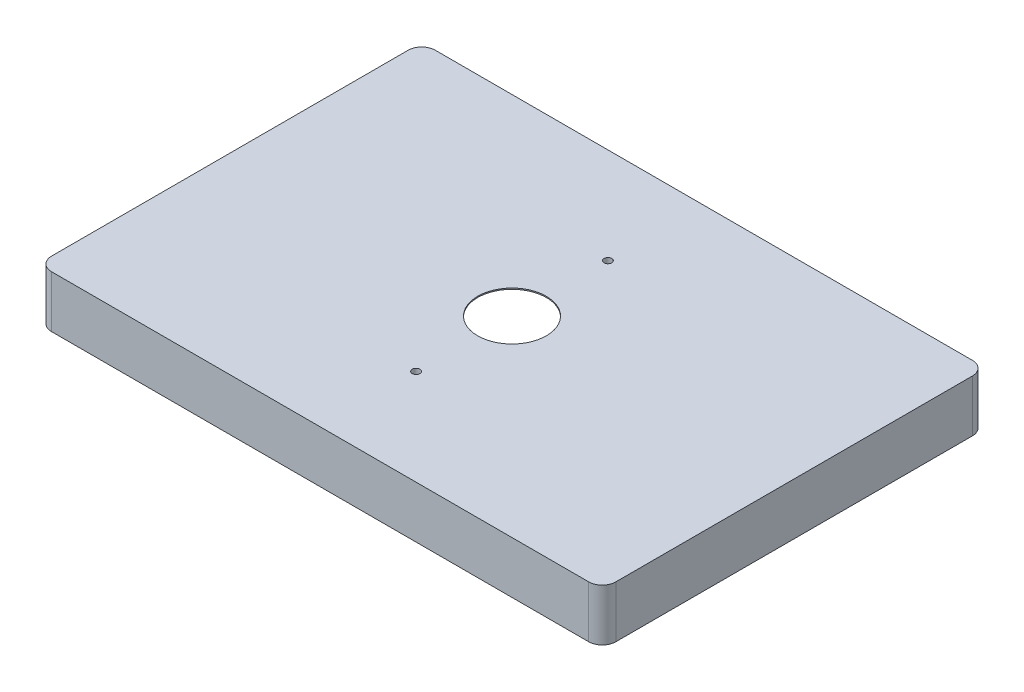
SolidWorks part; units mm, degrees
ref_plane "Front Plane" through (0, 0, 0) normal (0, 0, 1) x (1, 0, 0)
ref_plane "Top Plane" through (0, 0, 0) normal (0, 1, 0) x (1, 0, 0)
ref_plane "Right Plane" through (0, 0, 0) normal (1, 0, 0) x (0, 0, -1)
sketch "Sketch1" plane through (0, 0, 0) normal (0, 1, 0) x (1, 0, 0)
  line L1 (125, -85) -> (-125, -85)
  line L2 (125, -85) -> (125, 85)
  line L3 (125, 85) -> (-125, 85)
  line L4 (-125, -85) -> (-125, 85)
  line L5 (125, -85) -> (-125, 85) construction
  line L6 (125, 85) -> (-125, -85) construction
  circle A0 centre (0, 0) radius 15.2
  point P0 (0, 0)
  dimension "D3" = 30.4
  dimension "D1" = 170
  dimension "D2" = 250
extrude "Boss-Extrude1" add sketch "Sketch1" against normal blind 10
fillet "Fillet1" radius 6 4 edges at (-125, -5, -85) (-125, -5, 85) (125, -5, 85) (125, -5, -85)
sketch "Sketch3" plane through (0, -10, 0) normal (0, -1, 0) x (1, 0, 0)
  line L8 (-121, 79) -> (-121, -79)
  line L9 (-119, -81) -> (119, -81)
  line L10 (121, -79) -> (121, 79)
  line L11 (119, 81) -> (-119, 81)
  line L12 (-121, 79) -> (-121, -79)
  line L13 (-119, -81) -> (119, -81)
  line L14 (121, -79) -> (121, 79)
  line L15 (119, 81) -> (-119, 81)
  line L16 (-125, 79) -> (-125, -79)
  line L17 (-119, -85) -> (119, -85)
  line L18 (125, -79) -> (125, 79)
  line L19 (119, 85) -> (-119, 85)
  line L20 (-125, 79) -> (-125, -79)
  line L21 (-119, -85) -> (119, -85)
  line L22 (125, -79) -> (125, 79)
  line L23 (119, 85) -> (-119, 85)
  arc A4 (-121, -79) -> (-119, -81) centre (-119, -79) ccw
  arc A5 (119, -81) -> (121, -79) centre (119, -79) ccw
  arc A6 (121, 79) -> (119, 81) centre (119, 79) ccw
  arc A7 (-121, 79) -> (-119, 81) centre (-119, 79) cw
  arc A12 (-125, -79) -> (-119, -85) centre (-119, -79) ccw
  arc A13 (119, -85) -> (125, -79) centre (119, -79) ccw
  arc A14 (125, 79) -> (119, 85) centre (119, 79) ccw
  arc A15 (-119, 85) -> (-125, 79) centre (-119, 79) ccw
  arc A16 (-125, -79) -> (-119, -85) centre (-119, -79) ccw
  arc A17 (119, -85) -> (125, -79) centre (119, -79) ccw
  arc A18 (125, 79) -> (119, 85) centre (119, 79) ccw
  arc A19 (-119, 85) -> (-125, 79) centre (-119, 79) ccw
  arc A20 (-121, -79) -> (-119, -81) centre (-119, -79) ccw
  arc A21 (-121, -79) -> (-119, -81) centre (-119, -79) ccw
  arc A22 (119, -81) -> (121, -79) centre (119, -79) ccw
  arc A23 (119, -81) -> (121, -79) centre (119, -79) ccw
  arc A24 (121, 79) -> (119, 81) centre (119, 79) ccw
  arc A25 (121, 79) -> (119, 81) centre (119, 79) ccw
  arc A26 (-119, 81) -> (-121, 79) centre (-119, 79) ccw
  arc A27 (-119, 81) -> (-121, 79) centre (-119, 79) ccw
  line M14 (-125, 79) -> (-125, -79)
  arc M15 (-125, -79) -> (-119, -85) centre (-119, -79) ccw
  line M16 (-119, -85) -> (119, -85)
  arc M17 (119, -85) -> (125, -79) centre (119, -79) ccw
  line M18 (125, -79) -> (125, 79)
  arc M19 (125, 79) -> (119, 85) centre (119, 79) ccw
  line M20 (119, 85) -> (-119, 85)
  arc M21 (-119, 85) -> (-125, 79) centre (-119, 79) ccw
  dimension "D2" = 2
  dimension "D1" = 4
  dimension "D3" = 0
extrude "Boss-Extrude2" add sketch "Sketch3" along normal blind 13 contours L12 A7 L15 A6 L14 A5 L13 A4 M21 M14 M15 M16 M17 M18 M19 M20 | L20 A16 L21 A17 L22 A18 L23 A19
sketch "Sketch4" plane through (0, -10, 0) normal (0, -1, 0) x (1, 0, 0)
  line L0 (121, -50) -> (121, 50)
  line L5 (0, 30) -> (0, -30) construction
  line L7 (121, -79) -> (121, 79) construction
  line L8 (121, 50) -> (0, 30)
  line L9 (0, 0) -> (121, 0) construction
  line L10 (121, -50) -> (0, -30)
  circle A0 centre (0, 0) radius 15.2 construction
  circle A1 centre (0, 0) radius 15.2 construction
  arc A3 (0, -30) -> (0, 30) centre (4.9587, 0) cw
  point P3 (121, 0)
  dimension "D1" = 100
  dimension "D3" = 60
extrude "Cut-Extrude1" cut sketch "Sketch4" against normal blind 8
chamfer "Chamfer1" distance 5 distance2 1.5 1 edges at (0, -2, 15.2)
sketch "Sketch5" plane through (0, -10, 0) normal (0, -1, 0) x (1, 0, 0)
  line L0 (0, -42.5) -> (0, 42.5) construction
  point P5 (0, 0)
  point P7 (0, 42.5)
  point P8 (0, -42.5)
  dimension "D1" = 85
hole_wizard "CSK for M3 Hex Socket Countersunk Cap Screw1" positions "Sketch6" profile "Sketch7" countersink size "M3" standard "ISO" end condition through all
sketch "Sketch6" plane through (0, -10, 0) normal (0, -1, 0) x (-1, 0, 0)
  point P0 (0, 42.5)
  point P3 (0, -42.5)
sketch "Sketch7" plane through (0, -10, -42.5) normal (1, 0, 0) x (0, 0, -1)
  line L0 (0, 0) -> (0, 10)
  line L1 (0, 10) -> (1.7, 10)
  line L2 (1.7, 10) -> (1.7, 5.66)
  line L3 (1.7, 5.66) -> (3.36, 4)
  line L4 (3.36, 4) -> (3.36, 0)
  line L6 (3.36, 0) -> (0, 0)
  line L7 (-1.7, 5.66) -> (-3.36, 4) construction
  line L11 (0, -6.35) -> (0, 107.95) construction
  dimension "Thru Hole Dia." = 3.4
  dimension "Thru Hole Depth" = 10
  dimension "C'Sink Dia." = 6.72
  dimension "C'Sink Angle" = 90
  dimension "Head Clearance" = 4
chamfer "Chamfer2" distance 5 distance2 8 3 edges at (60.5, -10, -40) (-25.4484, -10, 0) (60.5, -10, 40)
sketch "Sketch8" plane through (121, 0, 0) normal (-1, 0, 0) x (0, 0, 1)
  line L0 (55.0678, -10) -> (50, -2) construction
  line L1 (-50, -2) -> (50, -2) construction
  line L2 (-50, -2) -> (-55.0678, -10) construction
  line L3 (55.0678, -10) -> (50, -2)
  line L4 (-50, -2) -> (50, -2)
  line L5 (-50, -2) -> (-55.0678, -10)
  line L6 (-55.0678, -10) -> (55.0678, -10) construction
  line L7 (-50, -18) -> (-55.0678, -10)
  line L8 (-50, -18) -> (50, -18)
  line L9 (55.0678, -10) -> (50, -18)
extrude "Cut-Extrude2" cut sketch "Sketch8" against normal blind 2
chamfer "Chamfer3" distance 2 angle 45 3 edges at (123, -14, -52.5339) (123, -18, 0) (123, -14, 52.5339)
fillet "Fillet2" radius 2 5 edges at (122, -17, -49.4497) (122, -17, 49.4497) (123, -5.0657, 51.942) (123, -5.0657, -51.942) (123, -2, 0)
